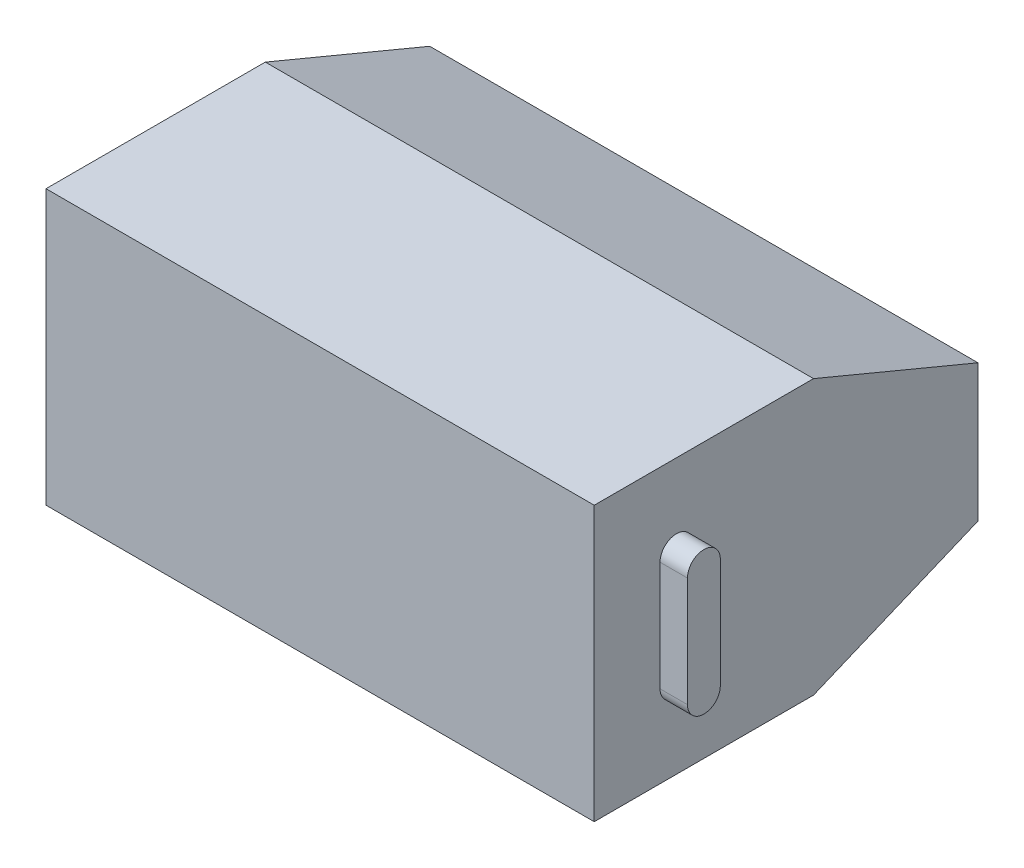
SolidWorks part; units mm, degrees
ref_plane "Front Plane" through (0, 0, 0) normal (0, 0, 1) x (1, 0, 0)
ref_plane "Top Plane" through (0, 0, 0) normal (0, 1, 0) x (1, 0, 0)
ref_plane "Right Plane" through (0, 0, 0) normal (1, 0, 0) x (0, 0, -1)
sketch "Sketch4" plane through (0, 0, 0) normal (1, 0, 0) x (0, 0, -1)
  point P0 (38.2598, 15.53)
  line B0 (0, 50) -> (40, 50)
  line B1 (0, 50) -> (0, 0)
  line B2 (0, 0) -> (40, 0)
  line B3 (40, 50) -> (40, 0) construction
  line B4 (40, 0) -> (70, 12.5)
  line B5 (70, 12.5) -> (70, 37.5)
  line B6 (70, 37.5) -> (40, 50)
  line B7 (18, 15) -> (18, 35)
  line B8 (15, 15) -> (15, 35) construction
  arc B9 (18, 35) -> (12, 35) centre (15, 35) ccw
  line B10 (12, 15) -> (12, 35)
  arc B11 (12, 15) -> (18, 15) centre (15, 15) ccw
  line B12 (15, 25) -> (0, 25) construction
sketch_block_instance "Brush-5"
sketch_block "Brush" parameters "D6"=6.6496, "D1"=50, "D2"=40, "D3"=30, "D4"=12.5, "D5"=12.5, "D7"=25.5148, "D8"=17.9174
sketch "Sketch2" plane through (0, 0, 0) normal (1, 0, 0) x (0, 0, -1)
  line L3 (70, 12.5) -> (70, 37.5) construction
  line L4 (40, 0) -> (70, 12.5) construction
  line L16 (0, 0) -> (40, 0) construction
  line L17 (0, 50) -> (0, 0) construction
  line L18 (0, 50) -> (40, 50) construction
  line L19 (70, 37.5) -> (40, 50) construction
  line L20 (70, 12.5) -> (70, 37.5)
  line L21 (40, 0) -> (70, 12.5)
  line L22 (0, 0) -> (40, 0)
  line L23 (0, 50) -> (0, 0)
  line L24 (0, 50) -> (40, 50)
  line L25 (70, 37.5) -> (40, 50)
extrude "Boss-Extrude1" add sketch "Sketch2" along normal blind 50 and the other way blind 50
sketch "Sketch3" plane through (0, 0, 0) normal (1, 0, 0) x (0, 0, -1)
  line L4 (18, 15) -> (18, 35) construction
  line L5 (12, 15) -> (12, 35) construction
  line L6 (18, 15) -> (18, 35)
  line L7 (12, 15) -> (12, 35)
  arc A4 (12, 15) -> (18, 15) centre (15, 15) ccw construction
  arc A5 (18, 35) -> (12, 35) centre (15, 35) ccw construction
  arc A6 (12, 15) -> (18, 15) centre (15, 15) ccw
  arc A7 (18, 35) -> (12, 35) centre (15, 35) ccw
extrude "Boss-Extrude2" add sketch "Sketch3" along normal blind 5 from surface starting at face at (50, 25, -36.6667)
extrude "Boss-Extrude3" add sketch "Sketch3<2>" against normal blind 5 from surface starting at face at (-50, 25, -36.6667)
sketch "Sketch3<2>" plane through (0, 0, 0) normal (1, 0, 0) x (0, 0, -1) same geometry as "Sketch3"
